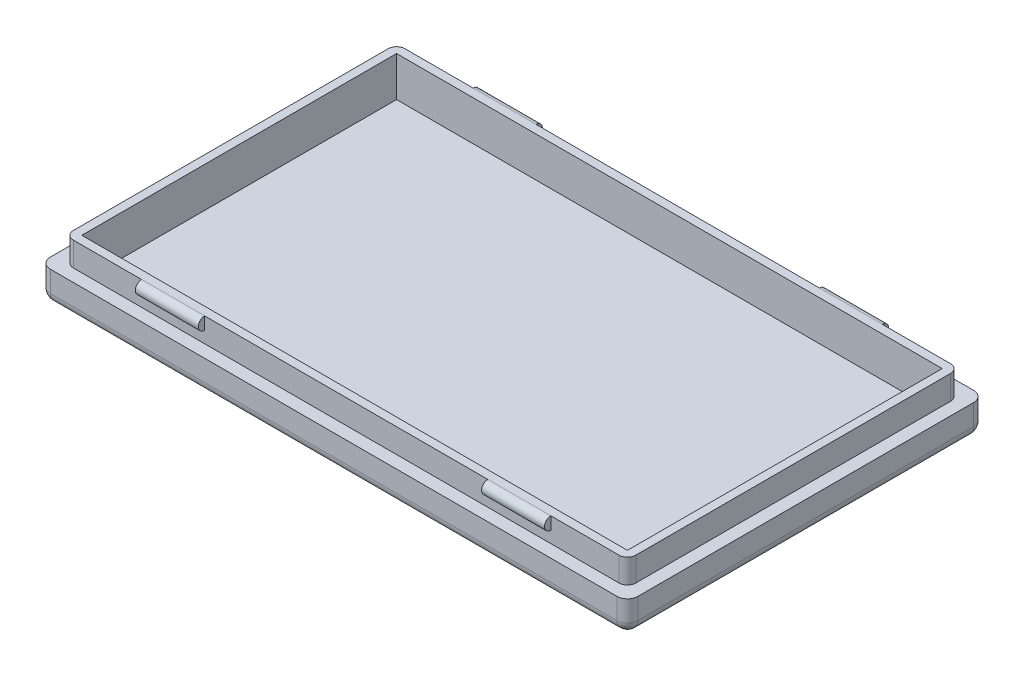
SolidWorks part; units mm, degrees
material "ABS"
ref_plane "Front Plane" through (0, 0, 0) normal (0, 0, 1) x (1, 0, 0)
ref_plane "Top Plane" through (0, 0, 0) normal (0, 1, 0) x (1, 0, 0)
ref_plane "Right Plane" through (0, 0, 0) normal (1, 0, 0) x (0, 0, -1)
sketch "Sketch1" plane through (0, 0, 0) normal (0, 1, 0) x (1, 0, 0)
  line L1 (28, -17) -> (-28, -17)
  line L2 (28, -17) -> (28, 17)
  line L3 (28, 17) -> (-28, 17)
  line L4 (-28, -17) -> (-28, 17)
  line L5 (28, -17) -> (-28, 17) construction
  line L6 (28, 17) -> (-28, -17) construction
  line L7 (26, -15) -> (-26, -15)
  line L8 (26, -15) -> (26, 15)
  line L9 (26, 15) -> (-26, 15)
  line L10 (-26, -15) -> (-26, 15)
  line L11 (26, -15) -> (-26, 15) construction
  line L12 (26, 15) -> (-26, -15) construction
  point P0 (0, 0)
  point P6 (0, 0)
  dimension "D1" = 56
  dimension "D2" = 34
  dimension "D3" = 2
  dimension "D4" = 2
extrude "Boss-Extrude1" add sketch "Sketch1" along normal blind 1.5 contours L10 L7 L8 L9 | L4 L1 L2 L3 L7 L10 L9 L8 region at (0, 0, 16.3449) region at (0, 0, 0)
extrude "Boss-Extrude2" add sketch "Sketch1<3>" along normal blind 3 contours L4 L1 L2 L3 L7 L10 L9 L8 region at (0, 0, 16.3449)
sketch "Sketch1<3>" plane through (0, 0, 0) normal (0, 1, 0) x (1, 0, 0) same geometry as "Sketch1"
sketch "Sketch2" plane through (0, 3, 0) normal (0, 1, 0) x (1, 0, 0)
  line L0 (26, 15) -> (26, -15) construction
  line L1 (-26, -15) -> (26, -15) construction
  line L2 (-26, -15) -> (-26, 15) construction
  line L3 (-26, 15) -> (26, 15) construction
  line L4 (26, 15) -> (26, -15)
  line L5 (-26, -15) -> (26, -15)
  line L6 (-26, -15) -> (-26, 15)
  line L7 (-26, 15) -> (26, 15)
  line L8 (-26.8, 15.8) -> (26.8, 15.8)
  line L9 (26.8, 15.8) -> (26.8, -15.8)
  line L10 (-26.8, -15.8) -> (26.8, -15.8)
  line L11 (-26.8, -15.8) -> (-26.8, 15.8)
  dimension "D1" = 0.8
extrude "Boss-Extrude3" add sketch "Sketch2" along normal blind 2.3
sketch "Sketch3" plane through (0, 3, 0) normal (0, 1, 0) x (1, 0, 0)
  line L0 (-28, -17) -> (-28, 17) construction
  line L1 (-28, -10.25) -> (-26.8, -10.25)
  line L2 (-28, -10.25) -> (-28, -6.5)
  line L3 (-28, -6.5) -> (-26.8, -6.5)
  line L4 (-26.8, -10.25) -> (-26.8, -6.5)
  line L5 (-26.8, 15.8) -> (-26.8, -15.8) construction
  line L6 (0, 0) -> (-10.9883, 0) construction
  line L7 (-28, 6.5) -> (-26.8, 6.5)
  line L8 (-26.8, 10.25) -> (-26.8, 6.5)
  line L9 (-28, 10.25) -> (-26.8, 10.25)
  line L10 (-28, 10.25) -> (-28, 6.5)
  dimension "D1" = 13
  dimension "D2" = 20.5
extrude "Cut-Extrude1" cut sketch "Sketch3" against normal blind 1
sketch "Sketch4" plane through (0, 0, 0) normal (1, 0, 0) x (0, 0, -1)
  line L0 (15.8, 5.3) -> (15.8, 3) construction
  line L1 (-15.8, 5.3) -> (-15.8, 3) construction
  circle A0 centre (15.8, 4.7) radius 0.6
  circle A1 centre (-15.8, 4.7) radius 0.6
  dimension "D1" = 1.2
extrude "Boss-Extrude4" add sketch "Sketch4" along normal blind 6 from offset 13.5
mirror "Mirror1" about plane through (0, 0, 0) normal (1, 0, 0) of "Boss-Extrude4"
fillet "Fillet1" radius 1 8 edges at (0, 0, 17) (28, 0, 0) (0, 0, -17) (-28, 0, 0) (28, 1.5, 17) (-28, 1.5, 17) (-28, 1.5, -17) (28, 1.5, -17)
fillet "Fillet2" radius 0.8 4 edges at (26.8, 4.15, 15.8) (-26.8, 4.15, 15.8) (-26.8, 4.15, -15.8) (26.8, 4.15, -15.8)
